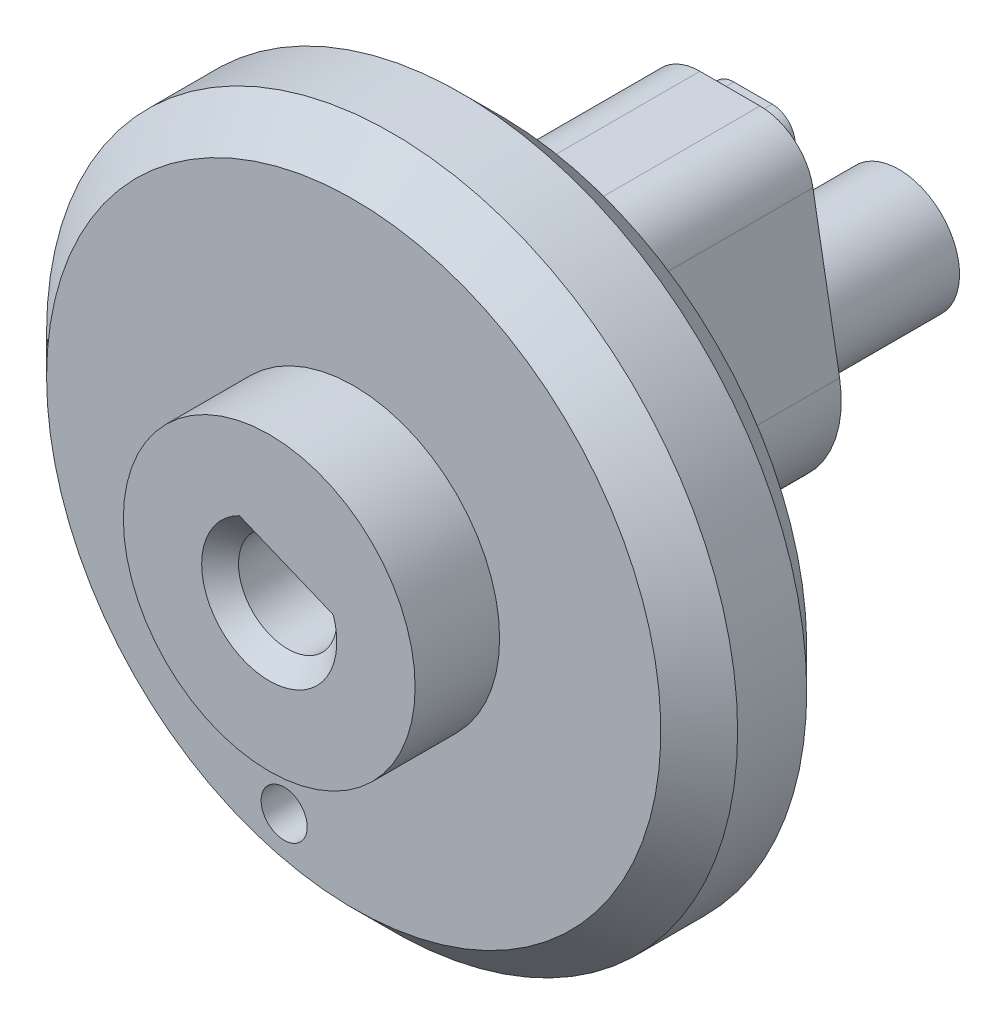
SolidWorks part; units mm, degrees
material "Zinc AG40A (Zn-4Al-0.4Mg; Zamak 3), Cast"
ref_plane "Front Plane" through (0, 0, 0) normal (0, 0, 1) x (1, 0, 0)
ref_plane "Top Plane" through (0, 0, 0) normal (0, 1, 0) x (1, 0, 0)
ref_plane "Right Plane" through (0, 0, 0) normal (1, 0, 0) x (0, 0, -1)
sketch "Sketch1" plane through (0, 0, 0) normal (0, 0, 1) x (1, 0, 0)
  line L0 (-1.2429, 3.556) -> (-1.8135, 0.3198)
  line L1 (-1.2429, 3.556) -> (1.2429, 3.556)
  line L2 (1.2429, 3.556) -> (1.8135, 0.3198)
  line L3 (0, 3.3051) -> (0, 0) construction
  arc A0 (-1.8135, 0.3198) -> (1.8135, 0.3198) centre (0, 0) ccw
  dimension "D1" = 3.683
  dimension "D2" = 10
  dimension "D3" = 10
  dimension "D4" = 3.556
extrude "Extrude1" add sketch "Sketch1" along normal blind 3.81
sketch "Sketch8" plane through (0, 0, 3.81) normal (0, 0, 1) x (1, 0, 0)
  circle A2 centre (0, 0) radius 2.413
  dimension "D1" = 4.826
extrude "Extrude8" add sketch "Sketch8" along normal blind 3.81
sketch "Sketch6" plane through (0, 0, 3.81) normal (0, 0, 1) x (1, 0, 0)
  circle A0 centre (0, 0) radius 5.715
  dimension "D1" = 11.43
extrude "Extrude6" add sketch "Sketch6" along normal blind 2.413
sketch "Sketch4" plane through (0, 0, 7.62) normal (0, 0, 1) x (1, 0, 0)
  circle A0 centre (0, 0) radius 0.254
  dimension "D1" = 0.508
extrude "Extrude4" cut sketch "Sketch4" against normal blind 6.731
sketch "Sketch5" plane through (0, 0, 0) normal (0, 0, -1) x (-1, 0, 0)
  circle A0 centre (0, 0) radius 1.0033
  dimension "D1" = 2.0066
extrude "Extrude5" add sketch "Sketch5" along normal blind 2.794
fillet "Fillet2" radius 0.889 2 edges at (-1.2429, 3.556, 1.905) (1.2429, 3.556, 1.905)
chamfer "Chamfer1" distance 0.635 angle 45 1 edges at (5.715, 0, 3.81)
sketch "Sketch7" plane through (0, 0, 6.223) normal (0, 0, 1) x (1, 0, 0)
  line L0 (-1.1505, -4.2935) -> (0, 0) construction
  line L1 (0, 0) -> (0, -3.6775) construction
  circle A0 centre (-1.1505, -4.2935) radius 0.381
  dimension "D2" = 0.762
  dimension "D1" = 15
  dimension "D3" = 4.445
extrude "Extrude7" cut sketch "Sketch7" against normal through all
chamfer "Chamfer3" distance 0.635 angle 45 1 edges at (5.715, 0, 6.223)
sketch "Sketch9" plane through (0, 0, 0) normal (0, 0, -1) x (-1, 0, 0)
  line L1 (-0.3175, 3.302) -> (0.3175, 3.302)
  line L2 (-0.6985, 2.921) -> (-0.6985, 0)
  line L3 (-0.6985, 0) -> (0.6985, 0)
  line L4 (0.6985, 2.921) -> (0.6985, 0)
  arc A0 (-0.3175, 3.302) -> (-0.6985, 2.921) centre (-0.3175, 2.921) ccw
  arc A1 (0.3175, 3.302) -> (0.6985, 2.921) centre (0.3175, 2.921) cw
  point P4 (0, 0)
  dimension "D3" = 0.381
  dimension "D1" = 1.397
  dimension "D2" = 3.302
extrude "Extrude9" add sketch "Sketch9" along normal blind 0.381
sketch "Sketch11" plane through (0, 0, 3.81) normal (0, 0, -1) x (-1, 0, 0)
  line L0 (1.8689, -3.5751) -> (3.0969, -4.8032)
  line L1 (0.1345, -5.7134) -> (3.0969, -5.7134)
  line L2 (3.0969, -5.7134) -> (3.0969, -4.8032)
  line L3 (0.1345, -5.7134) -> (0.1345, -4.2935)
  arc A0 (1.8689, -3.5751) -> (0.1345, -4.2935) centre (1.1505, -4.2935) ccw
  circle A1 centre (1.1505, -4.2935) radius 0.381 construction
  circle A2 centre (0, 0) radius 5.715 construction
  dimension "D2" = 1.016
  dimension "D1" = 45
extrude "Extrude10" cut sketch "Sketch11" against normal blind 1.397
sketch "Sketch17" plane through (0, 0, 7.62) normal (0, 0, 1) x (1, 0, 0)
  line L0 (0, 0) -> (0.4411, 1.0649) construction
  line L2 (0, 0) -> (0, 0.8128)
  line L4 (0, 0) -> (0.5747, 0.5747)
  circle A0 centre (0, 0) radius 0.7366 construction
  arc A1 (0.1537, 0.7981) -> (0.4557, 0.673) centre (0.3791, 0.9152) ccw
  arc A3 (0.5747, 0.5747) -> (0.4557, 0.673) centre (0, 0) ccw
  arc A4 (0.1537, 0.7981) -> (0, 0.8128) centre (0, 0) ccw
  dimension "D2" = 45
  dimension "D3" = 22.5
  dimension "D4" = 1.4732
  dimension "D1" = 0.508
  dimension "D6" = 1.6256
extrude "Extrude11" cut sketch "Sketch17" against normal blind 6.731
pattern_circular "CirPattern1" count 8 over 360 about axis through (0, 0, 7.62) along (0, 0, 1) of "Extrude11"
sketch "Sketch18" plane through (0, 0, 7.62) normal (0, 0, 1) x (1, 0, 0)
  line L0 (0, 0) -> (-0.3475, 0) construction
  line L1 (-0.5392, 0.6082) -> (0.8113, 0.0488)
  line L2 (-0.5392, 0.6082) -> (-0.3642, 1.0306)
  line L3 (-0.3642, 1.0306) -> (0.9863, 0.4712)
  line L4 (0.8113, 0.0488) -> (0.9863, 0.4712)
  arc A0 (-0.4557, 0.673) -> (-0.673, 0.4557) centre (0, 0) ccw construction
  arc A1 (0.673, 0.4557) -> (0.4557, 0.673) centre (0, 0) ccw construction
  arc A2 (0.7981, -0.1537) -> (0.7981, 0.1537) centre (0, 0) ccw construction
  arc A3 (-0.4599, 0.5754) -> (0.7321, 0.0817) centre (0, 0) cw construction
  arc A4 (0.1537, 0.7981) -> (0.4557, 0.673) centre (0.3791, 0.9152) ccw construction
  dimension "D1" = 0.381
  dimension "D2" = 22.5
extrude "Extrude12" add sketch "Sketch18" against normal up to surface (6.731 mm away) up to face at (0, 0, 0.889)
chamfer "Chamfer4" distance 0.381 angle 60 1 edges at (0.1361, 0.3285, 7.62) first distance on face at (-0.0964, -0.2328, 7.62)
sketch "Sketch19" plane through (0, 0, 7.62) normal (0, 0, 1) x (1, 0, 0)
  line L0 (0.8113, 0.0488) -> (-0.5392, 0.6082) construction
  line L1 (0.8113, 0.0488) -> (-0.5392, 0.6082)
  arc A0 (-0.7981, 0.1537) -> (-0.7981, -0.1537) centre (0, 0) ccw construction
  arc A1 (-0.5392, 0.6082) -> (0.8113, 0.0488) centre (0, 0) ccw
extrude "Extrude13" cut sketch "Sketch19" against normal blind 0.6604
sketch "Sketch20" plane through (0, 0, 0) normal (1, 0, 0) x (0, 0, -1)
  line L0 (-6.9596, -0.8128) -> (-6.9596, 0)
  line L1 (-6.9596, 0) -> (-6.1468, 0)
  line L2 (-6.1468, 0) -> (-6.9596, -0.8128)
  line L5 (-6.9596, -0.6612) -> (-6.9596, -0.7981) construction
  line L6 (-7.3896, 0) -> (-5.2833, 0) construction
  line L7 (-6.9596, -0.673) -> (-6.9596, -0.7981) construction
  dimension "D1" = 0.8128
  dimension "D2" = 45
revolve "Cut-Revolve1" cut sketch "Sketch20" angle 130 about L6 other way angle 90
ref_plane "Plane1" through (0, 0, 6.9601) normal (0, 0, 1) x (1, 0, 0)
ref_plane "Plane2" through (0, 0, 6.9601) normal (0, 0, 1) x (1, 0, 0)
sketch "Sketch21" plane through (0, 0, 6.9601) normal (0, 0, 1) x (1, 0, 0)
  line L0 (0.8113, 0.0488) -> (-0.5392, 0.6082) construction
  line L1 (-0.4599, 0.5754) -> (-0.5392, 0.6082)
  line L2 (0.7321, 0.0817) -> (0.8113, 0.0488)
  arc A0 (0.7321, 0.0817) -> (-0.4599, 0.5754) centre (0, 0) cw
  arc A1 (0.8113, 0.0488) -> (-0.5392, 0.6082) centre (0, 0) cw
  arc A2 (-0.0356, 0.812) -> (0.5993, 0.549) centre (0, 0) ccw construction
  dimension "D1" = 0.7366
extrude "Boss-Extrude1" add sketch "Sketch21" against normal up to surface (6.0711 mm away) up to face at (-0.0964, -0.2328, 0.889)
sketch "Sketch22" plane through (0, 0, 6.9601) normal (0, 0, 1) x (1, 0, 0)
  line L2 (-0.4599, 0.5754) -> (-0.5392, 0.6082)
  line L3 (0.8113, 0.0488) -> (0.7321, 0.0817)
  line L4 (-0.4599, 0.5754) -> (-0.5392, 0.6082)
  line L5 (0.8113, 0.0488) -> (0.7321, 0.0817)
  arc A2 (-0.4599, 0.5754) -> (0.7321, 0.0817) centre (0, 0) ccw
  arc A3 (-0.5392, 0.6082) -> (0.8113, 0.0488) centre (0, 0) ccw
  arc A4 (-0.4599, 0.5754) -> (0.7321, 0.0817) centre (0, 0) ccw
  arc A5 (-0.5392, 0.6082) -> (0.8113, 0.0488) centre (0, 0) ccw
  dimension "D1" = 0
extrude "Cut-Extrude1" cut sketch "Sketch22" against normal offset from surface (0.8387 mm away) 1.4986 up to face at (-0.0146, -0.0352, 7.62)
chamfer "Chamfer5" distance 0.1016 angle 45 1 edges at (-0.2819, -0.6805, 6.1214)
chamfer "Chamfer6" distance 0.3048 angle 45 1 edges at (-0.311, -0.7509, 7.62)
